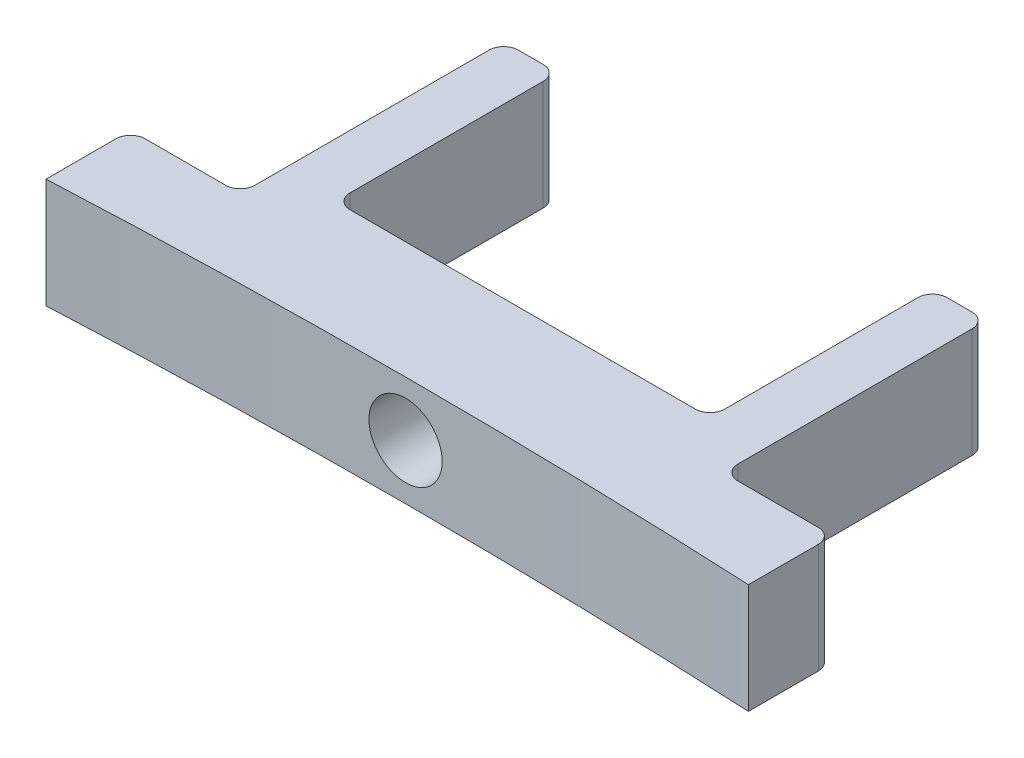
SolidWorks part; units mm, degrees
material "6061-T6 (SS)"
ref_plane "Front Plane" through (0, 0, 0) normal (0, 0, 1) x (1, 0, 0)
ref_plane "Top Plane" through (0, 0, 0) normal (0, 1, 0) x (1, 0, 0)
ref_plane "Right Plane" through (0, 0, 0) normal (1, 0, 0) x (0, 0, -1)
sketch "Sketch1" plane through (0, 0, 0) normal (0, 1, 0) x (1, 0, 0)
  line L0 (-12, 0) -> (0, 0)
  line L1 (24, -2.8) -> (24, -8.5763)
  line L2 (-24, -2.8) -> (-24, -8.5763)
  line L3 (-24, -8) -> (24, -8) construction
  line L4 (-12, 0) -> (-12, -2.8)
  line L5 (-12, -2.8) -> (-24, -2.8)
  line L6 (12, 0) -> (12, -2.8)
  line L7 (12, -2.8) -> (24, -2.8)
  line L22 (0, 0) -> (12, 0)
  line L25 (-24, -8.5763) -> (0, -508) construction
  line L26 (0, -508) -> (24, -8.5763) construction
  arc A0 (-24, -8.5763) -> (24, -8.5763) centre (0, -508) cw
  dimension "D1" = 8
  dimension "D2" = 500
  dimension "D3" = 2.8
  dimension "D4" = 12
  dimension "D5" = 48
extrude "Boss-Extrude1" add sketch "Sketch1" along normal blind 7.5
sketch "Sketch5" plane through (0, 7.5, 0) normal (0, 1, 0) x (1, 0, 0)
  line L0 (12, 0) -> (12.8, 0)
  line L1 (12.8, 0) -> (12.8, 15.2)
  line L2 (12.8, 15.2) -> (16.5, 15.2)
  line L3 (16.5, 15.2) -> (16.5, -2.8)
  line L4 (24, -2.8) -> (12, -2.8) construction
  line L6 (16.5, -2.8) -> (12, -2.8)
  line L7 (12, -2.8) -> (12, 0)
  line L8 (0, -4.125) -> (0, 4.125) construction
  line L9 (-12, -2.8) -> (-12, 0)
  line L10 (-16.5, -2.8) -> (-12, -2.8)
  line L11 (-16.5, 15.2) -> (-16.5, -2.8)
  line L12 (-12.8, 15.2) -> (-16.5, 15.2)
  line L13 (-12.8, 0) -> (-12.8, 15.2)
  line L14 (-12, 0) -> (-12.8, 0)
  dimension "D1" = 0.8
  dimension "D2" = 18
extrude "Boss-Extrude2" add sketch "Sketch5" against normal up to surface (7.5 mm away) up to face at (0, 0, 3.472)
fillet "Fillet1" radius 1 10 edges at (24, 3.75, 2.8) (-24, 3.75, 2.8) (16.5, 3.75, 2.8) (16.5, 3.75, -15.2) (12.8, 3.75, -15.2) (12.8, 3.75, 0) (-12.8, 3.75, 0) (-12.8, 3.75, -15.2) (-16.5, 3.75, -15.2) (-16.5, 3.75, 2.8)
ref_plane "MidPlane" through (0, 3.75, 0) normal (0, 1, 0) x (-1, 0, 0)
ref_plane "MidPlane2" through (0, 0, 0) normal (1, 0, 0) x (0, 0, -1)
ref_axis "CentralAxis" through (0, 3.75, 3.5669) along (0, 0, 1)
hole_wizard "M6x1.0 Tapped Hole1" positions "Sketch4" profile "Sketch3" tap size "M6x1.0" standard "ANSI Metric"
sketch "Sketch4" plane through (0, 0, 0) normal (0, 0, -1) x (-1, 0, 0)
  point P0 (0, 3.75)
cosmetic thread "Hole Thread1" parameters "D2"=6
sketch "Sketch3" plane through (0, 3.75, 0) normal (1, 0, 0) x (0, 1, 0)
  line L0 (0, 0) -> (0, 10.5022)
  line L1 (0, 10.5022) -> (2.5, 9)
  line L2 (2.5, 9) -> (2.5, 0)
  line L5 (2.5, 0) -> (0, 0)
  line L10 (0, 10.5022) -> (-2.5, 9) construction
  line L11 (0, -6.35) -> (0, 107.95) construction
  dimension "Tap Drill Dia." = 5
  dimension "Tap Drill Depth" = 9
  dimension "Drill Angle" = 118
sketch "Sketch7" plane through (0, 0, 0) normal (0, 0, -1) x (-1, 0, 0)
  line L0 (0, 0) -> (0, 3.75) construction
  line L1 (0, 3.75) -> (0, 7.5) construction
  line L2 (-11.8, 7.5) -> (11.8, 7.5) construction
  circle A0 centre (0, 3.75) radius 1.65
  dimension "D1" = 3.3
extrude "Cut-Extrude1" [suppressed] cut sketch "Sketch7" against normal through all
